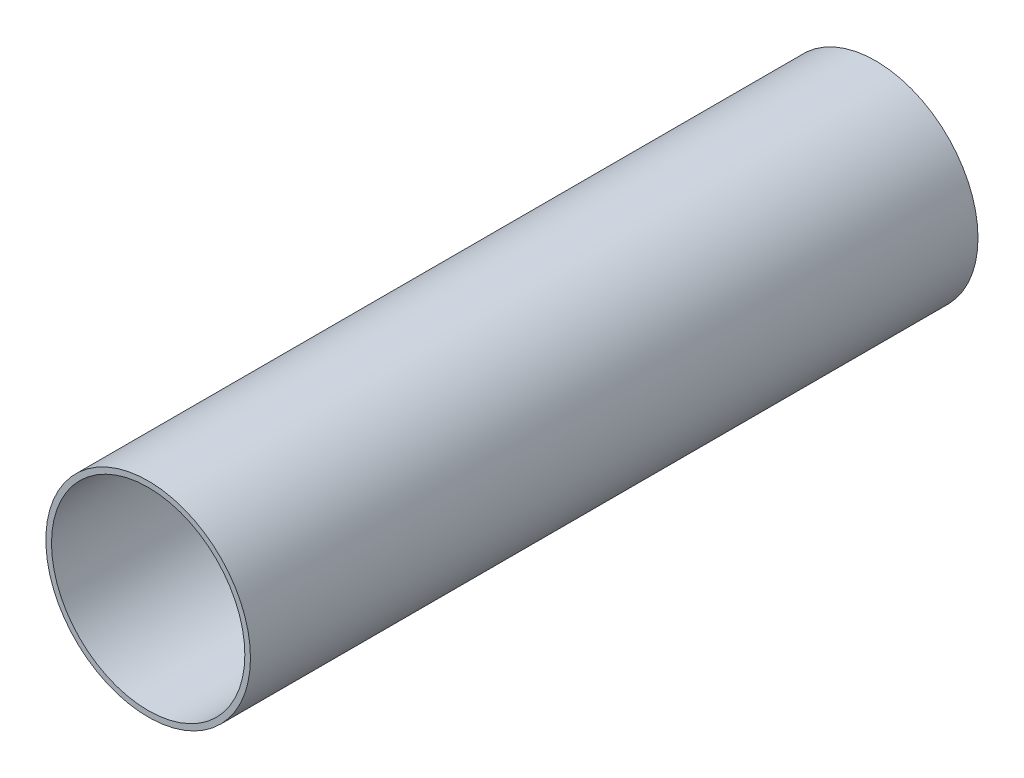
SolidWorks part; units mm, degrees
ref_plane "Front Plane" through (0, 0, 0) normal (0, 0, 1) x (1, 0, 0)
ref_plane "Top Plane" through (0, 0, 0) normal (0, 1, 0) x (1, 0, 0)
ref_plane "Right Plane" through (0, 0, 0) normal (1, 0, 0) x (0, 0, -1)
sketch "Sketch1" plane through (0, 0, 0) normal (0, 0, 1) x (1, 0, 0)
  circle A0 centre (0, 0) radius 28.575
  circle A1 centre (0, 0) radius 27.0002
  dimension "D1" = 54.0004
  dimension "D2" = 57.15
extrude "Boss-Extrude1" add sketch "Sketch1" along normal mid plane 203.2
equation "\"AIRFRAME_OD\"= 3.091in"
equation "\"AIRFRAME_ID\"= 3.00in"
equation "\"FLAT_T\" = 0.125in"
equation "\"NOSE_EXP_L\"= 3.5in"
equation "\"NOSE_SHOULDER_L\" = 5in"
equation "\"MAIN_L\" = 30in"
equation "\"RECO_COUP_L\" = 6in"
equation "\"RECO_SWITCH_L\" = 1.5in"
equation "\"DROGUE_L\" = 14in"
equation "\"ATS_FORE_COUP_L\" = 4in"
equation "\"ATS_AFT_COUP_L\" = 4in"
equation "\"LOWER_L\" = 16in"
equation "\"FIN_N\" = 4"
equation "\"CR_AFT_X\" = 0.5in"
equation "\"CR_FORE_X\" = 6in"
equation "\"D1@Sketch1\"=\"MOTOR_ID\""
equation "\"D2@Sketch1\"=\"MOTOR_OD\""
equation "\"D1@Boss-Extrude1\"=\"MOTOR_L\""
equation "\"FIN_ROOT\" = 5in"
equation "\"FIN_X\" = 0.75in"
equation "\"MOTOR_OD\" = 2.25in"
equation "\"MOTOR_ID\" = 2.126in"
equation "\"COUPLER_OD\" = 2.998in"
equation "\"COUPLER_ID\" = 2.875in"
equation "\"RECO_ROD_X\" = 1.5in"
equation "\"ATS_ROD_X\" = 2in"
equation "\"MOTOR_L\" = 8in"
